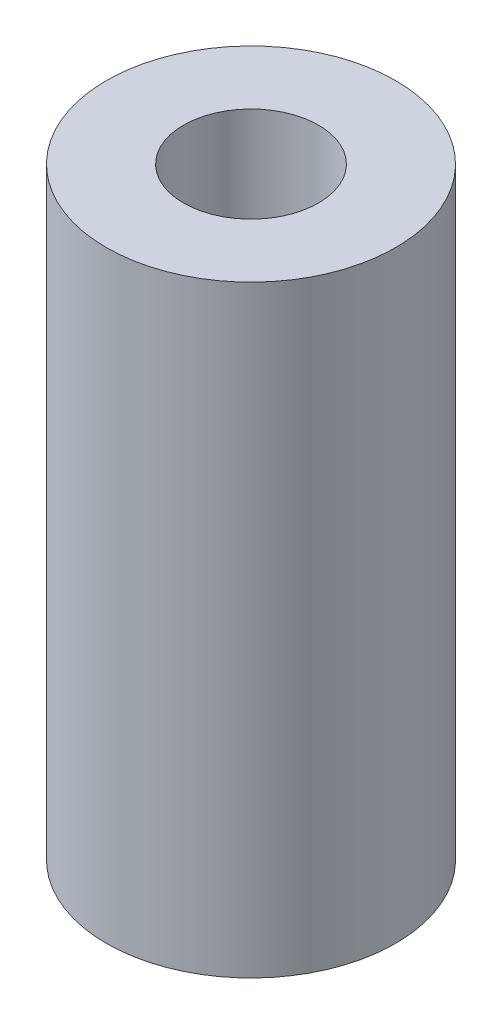
SolidWorks part; units mm, degrees
ref_plane "Front Plane" through (0, 0, 0) normal (0, 0, 1) x (1, 0, 0)
ref_plane "Top Plane" through (0, 0, 0) normal (0, 1, 0) x (1, 0, 0)
ref_plane "Right Plane" through (0, 0, 0) normal (1, 0, 0) x (0, 0, -1)
sketch "Sketch1" plane through (0, 0, 0) normal (0, 1, 0) x (1, 0, 0)
  line L0 (112.7539, 0.0419) -> (112.7539, -14.9581) construction
  line L1 (99.7539, 3.5419) -> (116.7539, 3.5419)
  line L2 (99.7539, 3.5419) -> (99.7539, -18.4581)
  line L3 (99.7539, -18.4581) -> (116.7539, -18.4581)
  line L4 (116.7539, 3.5419) -> (116.7539, -18.4581)
  line L7 (132.7539, 59.5419) -> (132.7539, -22.4581) construction
  line L8 (132.7539, -22.4581) -> (-17.2461, -22.4581) construction
  circle A1 centre (112.7539, -14.9581) radius 3
  point P8 (116.7539, -7.4581)
  point P9 (112.7539, -7.4581)
  point P11 (0, 0)
  point P14 (0, 0)
  dimension "D5" = 6
  dimension "D1" = 17
  dimension "D2" = 22
  dimension "D3" = 15
  dimension "D4" = 4
  dimension "D6" = 7.5
  dimension "D7" = 20
extrude "Boss-Extrude1" add sketch "Sketch1" along normal blind 12.5 contours A1 region at (112.7539, 0, 14.9581)
sketch "Sketch2" plane through (0, 12.5, 0) normal (0, 1, 0) x (1, 0, 0)
  circle A2 centre (112.7539, -14.9581) radius 1.4
  dimension "D1" = 2.8
extrude "Cut-Extrude1" cut sketch "Sketch2" against normal blind 10 contours A2
